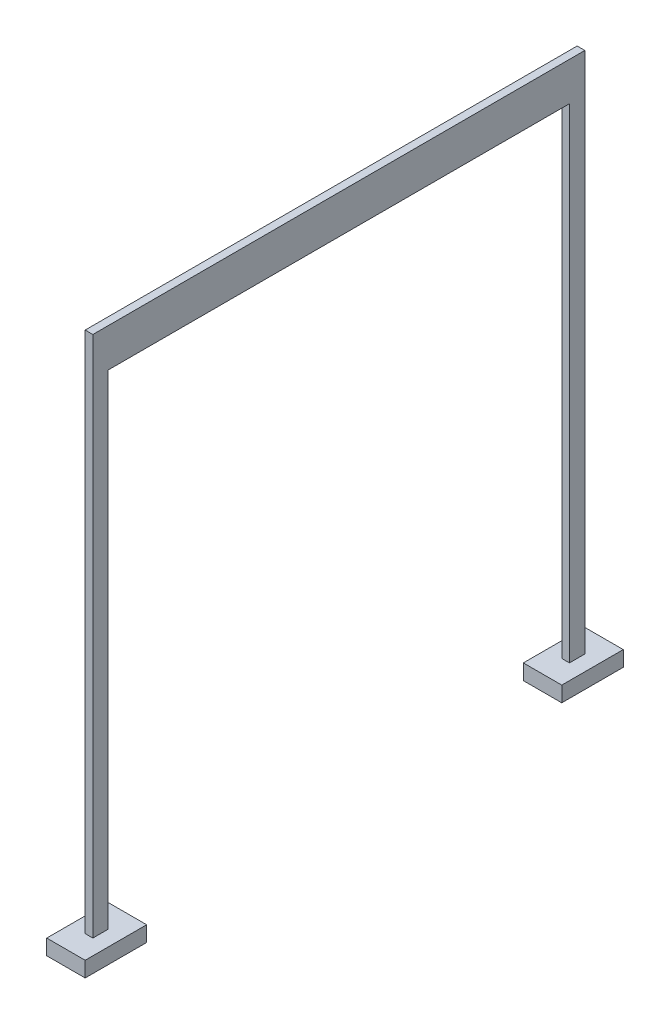
SolidWorks part; units mm, degrees
ref_plane "前视基准面" through (0, 0, 0) normal (0, 0, 1) x (1, 0, 0)
ref_plane "上视基准面" through (0, 0, 0) normal (0, 1, 0) x (1, 0, 0)
ref_plane "右视基准面" through (0, 0, 0) normal (1, 0, 0) x (0, 0, -1)
sketch "草图1" plane through (0, 0, 0) normal (1, 0, 0) x (0, 0, -1)
  line L0 (0, 0) -> (0, 395.5617) construction
  line L1 (320, 25) -> (320, -675)
  line L2 (-300, -25) -> (300, -25)
  line L3 (-300, -25) -> (-300, 25)
  line L4 (-300, 25) -> (300, 25)
  line L5 (300, -25) -> (300, 25)
  line L6 (-300, -25) -> (300, 25) construction
  line L7 (-300, 25) -> (300, -25) construction
  line L8 (-300, 25) -> (-320, 25)
  line L9 (-300, 25) -> (-300, -675)
  line L10 (-300, -675) -> (-320, -675)
  line L11 (-320, 25) -> (-320, -675)
  line L12 (300, -675) -> (320, -675)
  line L13 (300, 25) -> (300, -675)
  line L14 (300, 25) -> (320, 25)
  line L15 (300, -25) -> (300, 25)
  line L16 (-310, -675) -> (-310, -709.691) construction
  line L17 (350, -675) -> (270, -655) construction
  line L18 (-350, -655) -> (-270, -655)
  line L19 (-350, -655) -> (-350, -675)
  line L20 (-350, -675) -> (-270, -675)
  line L21 (-270, -655) -> (-270, -675)
  line L22 (-350, -655) -> (-270, -675) construction
  line L23 (-350, -675) -> (-270, -655) construction
  line L24 (350, -655) -> (270, -675) construction
  line L25 (270, -655) -> (270, -675)
  line L26 (350, -675) -> (270, -675)
  line L27 (350, -655) -> (350, -675)
  line L28 (350, -655) -> (270, -655)
  line L29 (300, -675) -> (320, -675)
  point P15 (-310, -665)
  point P20 (0, 0)
  point P25 (310, -665)
  dimension "D1" = 640
  dimension "D2" = 600
  dimension "D3" = 700
  dimension "D4" = 50
  dimension "D5" = 20
  dimension "D6" = 80
extrude "凸台-拉伸1" add sketch "草图1" along normal mid plane 10 contours L11 L18 L9 L3 L8 | L2 L5 L4 L3 | L28 L1 L14 L5 L13 | L21 L18 L9 L20 | L18 L11 L10 L9 | L19 L20 L11 L18 | L1 L28 L13 L12 | L27 L28 L1 L26 | L13 L28 L25 L26 region at (0, -315, -310) region at (0, -665, -335) region at (0, -665, -310) region at (0, 0, 0) region at (0, -665, -285) region at (0, -315, 310) region at (0, -665, 285) region at (0, -665, 310) region at (0, -665, 335)
extrude "凸台-拉伸2" add sketch "草图1<3>" along normal mid plane 50 contours L19 L20 L11 L18 | L18 L11 L10 L9 | L21 L18 L9 L20 | L13 L28 L25 L26 | L1 L28 L13 L12 | L27 L28 L1 L26 region at (0, -665, -335) region at (0, -665, -310) region at (0, -665, -285) region at (0, -665, 285) region at (0, -665, 310) region at (0, -665, 335)
sketch "草图1<3>" plane through (0, 0, 0) normal (1, 0, 0) x (0, 0, -1) same geometry as "草图1"
